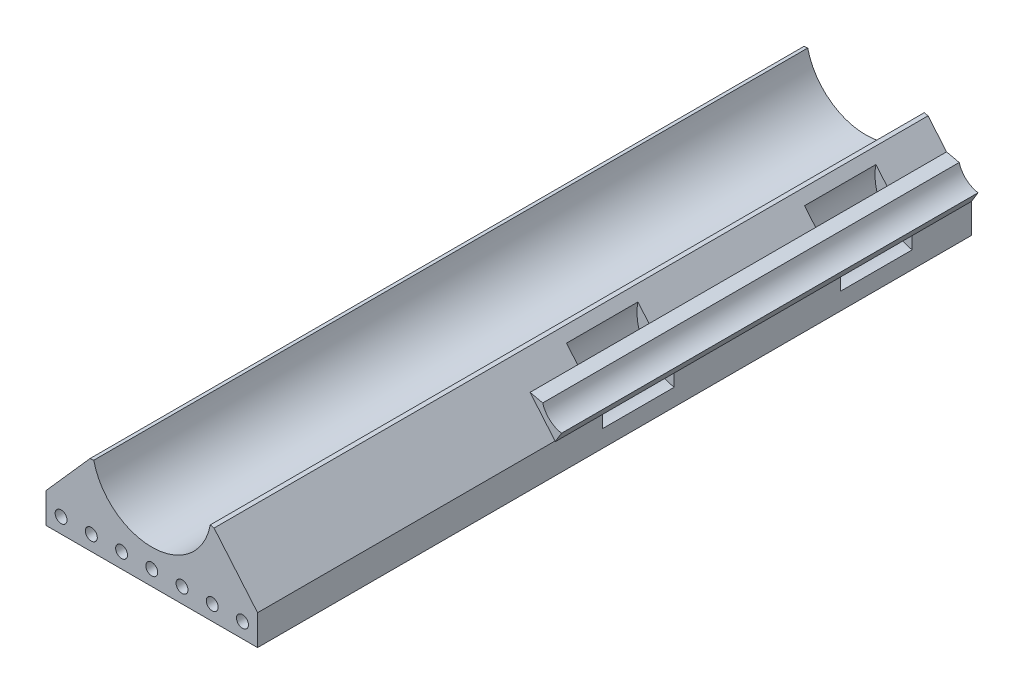
SolidWorks part; units mm, degrees
ref_plane "Front Plane" through (0, 0, 0) normal (0, 0, 1) x (1, 0, 0)
ref_plane "Top Plane" through (0, 0, 0) normal (0, 1, 0) x (1, 0, 0)
ref_plane "Right Plane" through (0, 0, 0) normal (1, 0, 0) x (0, 0, -1)
sketch "Sketch1" plane through (0, 0, 0) normal (0, 0, 1) x (1, 0, 0)
  line L0 (-8.89, -5.3274) -> (8.89, -5.3274)
  line L1 (-5.2003, -1.1566) -> (-4.8752, -1.1102)
  line L2 (4.9138, -0.9244) -> (5.234, -0.9931)
  line L3 (5.234, -0.9931) -> (8.89, -5.3274)
  line L4 (-5.2003, -1.1566) -> (-8.89, -5.3274)
  line L6 (-8.89, -7.8674) -> (8.89, -7.8674)
  line L7 (-8.89, -7.8674) -> (-8.89, -5.3274)
  line L8 (-8.89, -5.3274) -> (8.89, -5.3274)
  line L9 (8.89, -7.8674) -> (8.89, -5.3274)
  line L10 (-8.89, -7.8674) -> (8.89, -5.3274) construction
  line L11 (-8.89, -5.3274) -> (8.89, -7.8674) construction
  arc A0 (-4.8752, -1.1102) -> (4.9138, -0.9244) centre (0, 0) ccw
  arc A1 (-5.2003, -1.1566) -> (5.234, -0.9931) centre (0, 0) ccw
  circle A2 centre (-7.62, -6.5974) radius 0.5
  circle A3 centre (-5.08, -6.5974) radius 0.5
  circle A4 centre (-2.54, -6.5974) radius 0.5
  circle A5 centre (0, -6.5974) radius 0.5
  circle A6 centre (2.54, -6.5974) radius 0.5
  circle A7 centre (5.08, -6.5974) radius 0.5
  circle A8 centre (7.62, -6.5974) radius 0.5
  point P8 (0, -5.3274)
  point P9 (0, -6.5974)
  dimension "D3" = 5
  dimension "1" = 1
  dimension "D2" = 2.54
  dimension "D4" = 2.54
  dimension "D5" = 1.27
  dimension "D1" = 7
extrude "Boss-Extrude1" add sketch "Sketch1" along normal blind 60 contours L1 A1 L2 A0 | A1 L4 L0 | L6 L9 L8 L0 L7 A8 A7 A6 A5 A4 A3 A2 | A1 L8 L3 region at (-5.4238, -4.0687, 0) region at (-4.445, -5.507, 0) region at (5.4517, -4.0256, 0) region at (-3.2623, -4.0675, 0)
sketch "Sketch2" plane through (0, 0, 0) normal (0, 0, 1) x (1, 0, 0)
  line L0 (9.4324, -4.4941) -> (8.89, -5.3903)
  line L1 (7.852, -3.0783) -> (6.79, -2.8378)
  line L2 (5.8535, -1.7275) -> (6.79, -2.8378)
  line L3 (8.89, -6.4246) -> (8.89, -5.3903)
  line L4 (8.89, -7.8674) -> (8.89, -5.3274) construction
  line L5 (5.234, -0.9931) -> (8.89, -5.3274) construction
  arc A0 (7.852, -3.0783) -> (9.4324, -4.4941) centre (9.7735, -2.5234) ccw
  arc A1 (8.89, -6.4246) -> (5.8535, -1.7275) centre (9.7735, -2.5234) cw
  arc A2 (6.79, -2.8378) -> (8.89, -5.3903) centre (9.7735, -2.5234) ccw
  point P11 (10.3013, -2.7425)
  point P12 (8.0694, -2.9472)
  point P13 (7.8713, -3.0595)
  point P14 (9.74, -3.0067)
  point P15 (8.89, -5.4617)
  point P16 (8.89, -5.4598)
  point P17 (7.1047, -3.2109)
  point P18 (9.4165, -4.5204)
  point P19 (6.79, -2.8378)
  dimension "D1" = 2
  dimension "D2" = 3
  dimension "D3" = 4
ref_plane "Plane1" through (0, 0, 8) normal (0, 0, -1) x (-1, 0, 0)
ref_plane "Plane2" through (0, 0, 28) normal (0, 0, -1) x (-1, 0, 0)
extrude "Cut-Extrude1" cut sketch "Sketch2" against normal mid plane 6 from surface contours A2 L2 A1 L3 region at (7.1126, -4.4007, 0) starting at plane "Plane1"
extrude "Cut-Extrude2" cut sketch "Sketch2<3>" against normal mid plane 6 from surface contours A2 L2 A1 L3 region at (7.1126, -4.4007, 0) starting at plane "Plane2"
sketch "Sketch2<3>" plane through (0, 0, 0) normal (0, 0, 1) x (1, 0, 0) same geometry as "Sketch2"
extrude "Boss-Extrude2" add sketch "Sketch2<4>" along normal blind 35 contours L1 A2 L0 A0 region at (8.0084, -4.1455, 0)
sketch "Sketch2<4>" plane through (0, 0, 0) normal (0, 0, 1) x (1, 0, 0) same geometry as "Sketch2"
